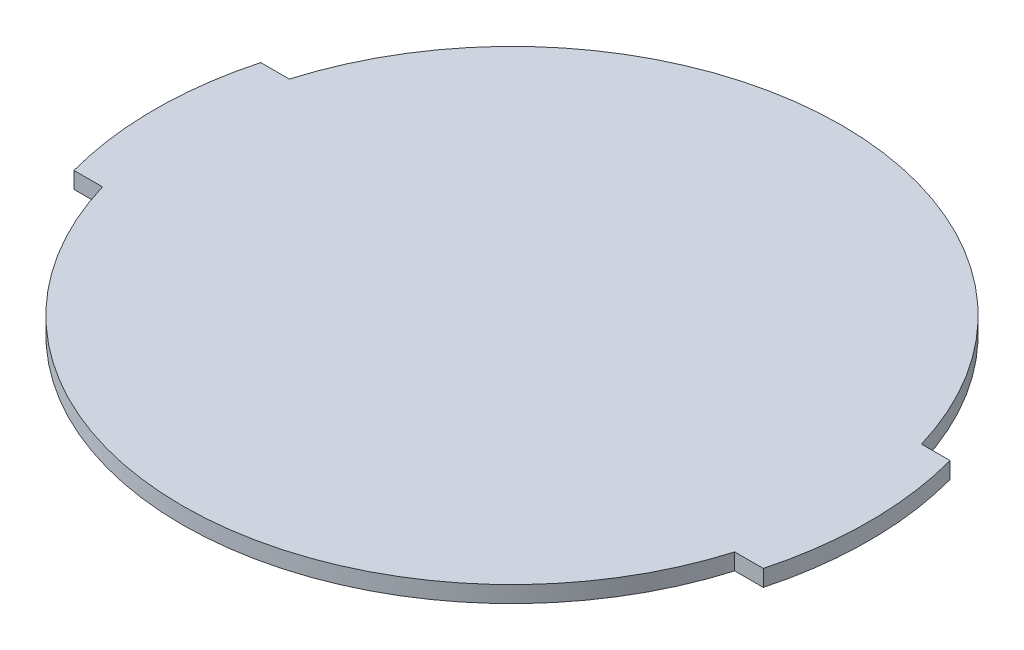
SolidWorks part; units mm, degrees
ref_plane "Front Plane" through (0, 0, 0) normal (0, 0, 1) x (1, 0, 0)
ref_plane "Top Plane" through (0, 0, 0) normal (0, 1, 0) x (1, 0, 0)
ref_plane "Right Plane" through (0, 0, 0) normal (1, 0, 0) x (0, 0, -1)
sketch "Sketch1" plane through (0, 0, 0) normal (0, 1, 0) x (1, 0, 0)
  line L0 (-62.7375, -17) -> (-57.5413, -17)
  line L1 (-62.7375, 17) -> (-57.5413, 17)
  line L2 (57.5413, 17) -> (62.7375, 17)
  line L3 (57.5413, -17) -> (62.7375, -17)
  line L4 (-32.8165, 0) -> (120.6229, 0) construction
  arc A0 (-57.5413, -17) -> (57.5413, -17) centre (0, 0) ccw
  arc A1 (-62.7375, 17) -> (-62.7375, -17) centre (0, 0) ccw
  arc A2 (62.7375, -17) -> (62.7375, 17) centre (0, 0) ccw
  arc A3 (57.5413, 17) -> (-57.5413, 17) centre (0, 0) ccw
  dimension "D1" = 120
  dimension "D6" = 130
  dimension "D2" = 17
  dimension "D3" = 17
  dimension "D4" = 17
  dimension "D5" = 17
extrude "Boss-Extrude1" add sketch "Sketch1" along normal blind 3
